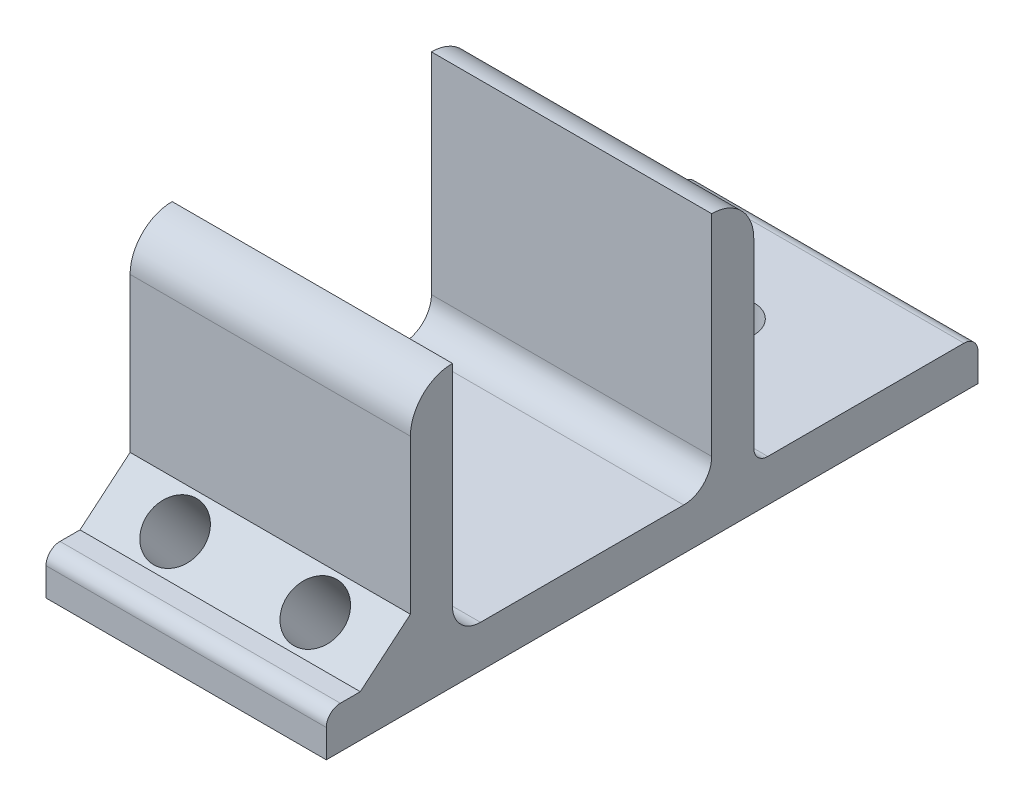
SolidWorks part; units mm, degrees
ref_plane "Plano frontal" through (0, 0, 0) normal (0, 0, 1) x (1, 0, 0)
ref_plane "Plano superior" through (0, 0, 0) normal (0, 1, 0) x (1, 0, 0)
ref_plane "Plano direito" through (0, 0, 0) normal (1, 0, 0) x (0, 0, -1)
sketch "Esboço2" plane through (0, 0, 0) normal (1, 0, 0) x (0, 0, -1)
  line L0 (-18.25, 0) -> (18.25, 0)
  line L1 (0, 26.0677) -> (0, 0) construction
  line L2 (-12.25, 17) -> (-12.25, 3)
  line L3 (9.25, 3) -> (-9.25, 3)
  line L4 (-9.25, 3) -> (-9.25, 20)
  line L5 (-18.25, 0) -> (-18.25, 2)
  line L6 (-17.25, 3) -> (-12.25, 3)
  line L7 (27.25, 3) -> (13.25, 3)
  line L8 (18.25, 0) -> (28.25, 0)
  line L9 (9.25, 3) -> (9.25, 20)
  line L10 (12.25, 17) -> (12.25, 4)
  line L11 (28.25, 0) -> (28.25, 2)
  arc A1 (-9.25, 20) -> (-12.25, 17) centre (-9.25, 17) ccw
  arc A2 (-18.25, 2) -> (-17.25, 3) centre (-17.25, 2) cw
  arc A3 (28.25, 2) -> (27.25, 3) centre (27.25, 2) ccw
  arc A4 (9.25, 20) -> (12.25, 17) centre (9.25, 17) cw
  arc A5 (12.25, 4) -> (13.25, 3) centre (13.25, 4) ccw
  point P26 (0, 3)
  dimension "D5" = 1
  dimension "D6" = 1
  dimension "D1" = 18.5
  dimension "D2" = 3
  dimension "D3" = 20
  dimension "D4" = 3
  dimension "D7" = 10
  dimension "D8" = 6
extrude "Ressalto-extrusão1" add sketch "Esboço2" along normal blind 20
fillet "Filete12" radius 2 2 edges at (10, 3, 9.25) (10, 3, -9.25)
chamfer "Chanfro1" distance 3 angle 50 1 edges at (10, 3, 12.25) first distance on face at (10, 10, 12.25)
sketch "Esboço3" plane through (0, 9.5529, 8.0158) normal (0, 0.766, 0.6428) x (1, 0, 0)
  line L0 (0, -7.8609) -> (20, -7.8609) construction
  line L1 (0, -10.1945) -> (0, -5.5273) construction
  line L2 (20, -5.5273) -> (20, -10.1945) construction
  line L3 (10, -5.5273) -> (10, -10.1945) construction
  line L4 (0, -5.5273) -> (20, -5.5273) construction
  line L5 (20, -10.1945) -> (0, -10.1945) construction
  circle A0 centre (5, -7.8609) radius 2
  circle A1 centre (15, -7.8609) radius 2
  dimension "D1" = 4
  dimension "D2" = 10
extrude "Corte-extrusão1" cut sketch "Esboço3" against normal through all
sketch "Esboço4" plane through (0, 3, 0) normal (0, 1, 0) x (1, 0, 0)
  line L0 (20, 27.25) -> (0, 27.25) construction
  line L1 (0, 27.25) -> (0, 13.25) construction
  circle A0 centre (10, 20.25) radius 2
  point P4 (10, 27.25)
  point P7 (0, 20.25)
  dimension "D1" = 4
extrude "Corte-extrusão2" cut sketch "Esboço4" against normal blind 10
